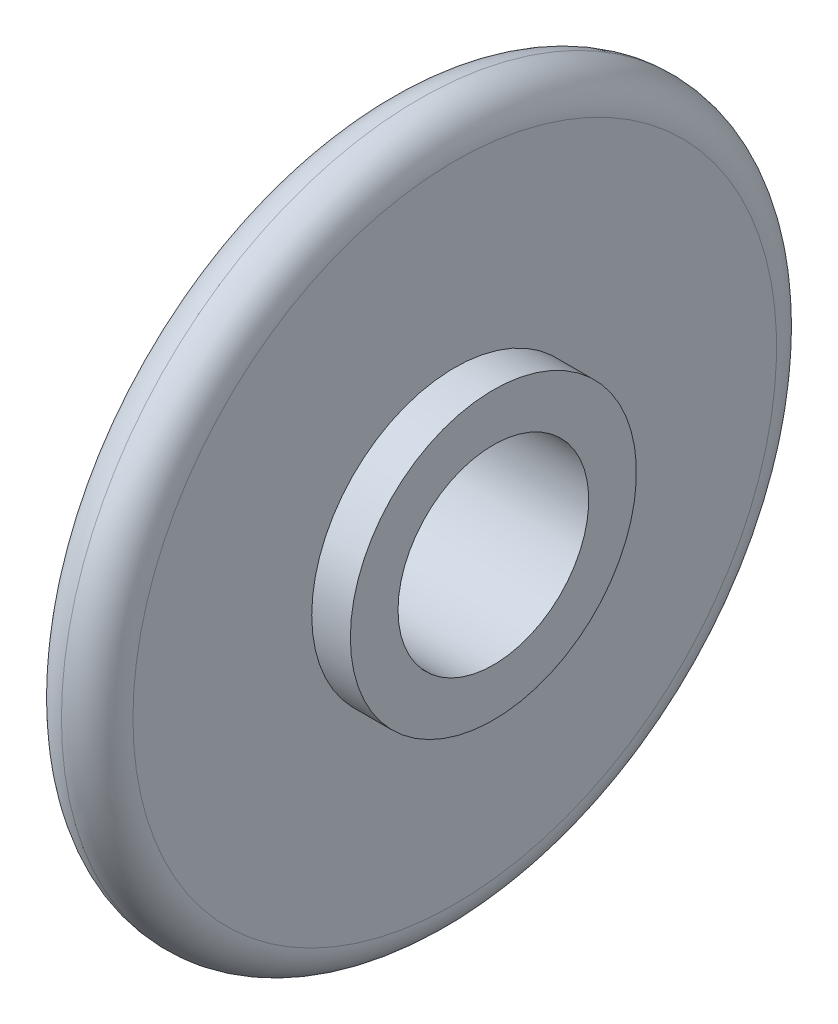
SolidWorks part; units mm, degrees
material "尼龙 101"
ref_plane "前视基准面" through (0, 0, 0) normal (0, 0, 1) x (1, 0, 0)
ref_plane "上视基准面" through (0, 0, 0) normal (0, 1, 0) x (1, 0, 0)
ref_plane "右视基准面" through (0, 0, 0) normal (1, 0, 0) x (0, 0, -1)
sketch "草图1" plane through (0, 0, 0) normal (0, 0, 1) x (1, 0, 0)
  line L0 (-24.3317, 0) -> (27.5428, 0) construction
  line L1 (-12.1551, 4) -> (-5.9151, 4)
  line L2 (-5.9151, 4) -> (-5.9151, 6)
  line L3 (-5.9151, 6) -> (-7.5351, 6)
  line L4 (-7.5351, 6) -> (-7.5351, 15)
  line L5 (-7.5351, 15) -> (-10.5351, 15)
  line L6 (-10.5351, 15) -> (-10.5351, 6)
  line L7 (-10.5351, 6) -> (-12.1551, 6)
  line L8 (-12.1551, 6) -> (-12.1551, 4)
  dimension "D1" = 8
  dimension "D2" = 12
  dimension "D3" = 30
  dimension "D4" = 12
  dimension "D5" = 1.62
  dimension "D6" = 1.62
  dimension "D7" = 3
revolve "旋转2" add sketch "草图1" angle 360 about L0
fillet "圆角1" radius 1.5 2 edges at (-7.5351, 0, 15) (-10.5351, 0, 15)
